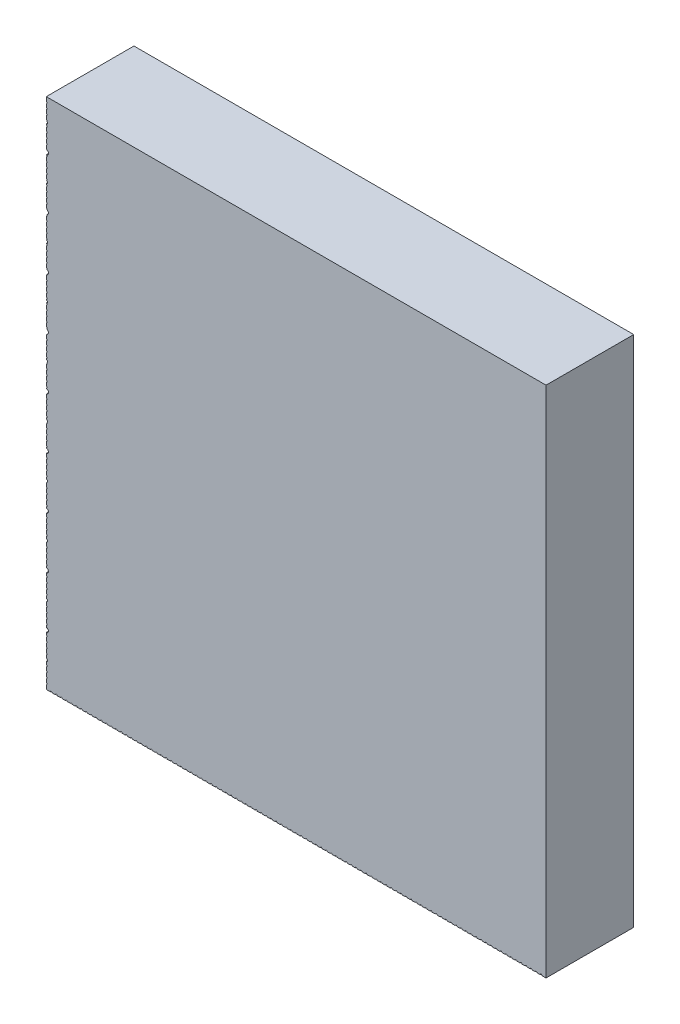
SolidWorks part; units mm, degrees
ref_plane "Front Plane" through (0, 0, 0) normal (0, 0, 1) x (1, 0, 0)
ref_plane "Top Plane" through (0, 0, 0) normal (0, 1, 0) x (1, 0, 0)
ref_plane "Right Plane" through (0, 0, 0) normal (1, 0, 0) x (0, 0, -1)
sketch "Sketch4" plane through (0, 0, 0) normal (0, 0, 1) x (1, 0, 0)
  line L1 (0, 0) -> (57, 0)
  line L2 (0, 0) -> (0, 58.5576)
  line L3 (0, 58.5576) -> (57, 58.5576)
  line L4 (57, 0) -> (57, 58.5576)
  spline S0 degree 1 poles (-4.6634, -4.7909) (51.2978, 52.6996) knots 0 0 1 1 construction
  spline S1 degree 1 poles (0, 0) (46.6344, 47.9087) knots 0.083333 0.083333 0.916667 0.916667 construction
  dimension "D1" = 57
  dimension "D2" = 58.5576
sketch "Sketch10" plane through (0, 0, 0) normal (0, 1, 0) x (1, 0, 0)
extrude "Boss-Extrude2" add sketch "Sketch4" along normal blind 10
sketch "Sketch14" plane through (0, 0, 10) normal (0, 0, 1) x (1, 0, 0)
  line L0 (0, 0) -> (57, 0) construction
  circle A0 centre (0.57, 0) radius 0.1
  spline S0 degree 1 poles (-5.7, -5.8558) (62.7, 64.4134) knots 0 0 1 1 construction
  spline S1 degree 1 poles (0, 0) (57, 58.5576) knots 0.083333 0.083333 0.916667 0.916667
  line M4 (0, 0) -> (57, 0)
  dimension "D1" = 0.2
  dimension "D2" = 0.57
extrude "Cut-Extrude1" cut sketch "Sketch14" against normal blind 10 contours A0 M4 region at (0.57, 0.0424, 10)
pattern_linear "LPattern1" count 99 spacing 0.57 along (1, 0, 0) of "Cut-Extrude1"
sketch "Sketch15" plane through (0, 0, 10) normal (0, 0, 1) x (1, 0, 0)
  line L0 (0.57, 0) -> (0.57, 0.5856)
  line L1 (0.57, 0.5856) -> (0, 0.5856)
  line L2 (0, 58.5576) -> (0, 0) construction
  circle A0 centre (0, 0.5856) radius 0.1
  spline S0 degree 1 poles (-5.7, -5.8558) (62.7, 64.4134) knots 0 0 1 1 construction
  spline S1 degree 1 poles (0, 0) (57, 58.5576) knots 0.083333 0.083333 0.916667 0.916667
  dimension "D1" = 0.2
extrude "Cut-Extrude2" cut sketch "Sketch15" against normal blind 10 contours A0 region at (-0.0972, 0.5856, 10)
pattern_linear "LPattern2" count 99 spacing 0.5856 along (0, 1, 0) of "Cut-Extrude2"
sketch "Sketch16" plane through (0, 0, 10) normal (0, 0, 1) x (1, 0, 0)
  circle A0 centre (0, 2.9279) radius 0.15
  dimension "D1" = 0.3
extrude "Cut-Extrude3" cut sketch "Sketch16" against normal blind 10
pattern_linear "LPattern3" count 19 spacing 2.95 along (0, 1, 0) of "Cut-Extrude3"
sketch "Sketch17" plane through (0, 0, 10) normal (0, 0, 1) x (1, 0, 0)
  circle A0 centre (0, 5.8779) radius 0.25
  dimension "D1" = 0.5
extrude "Cut-Extrude4" cut sketch "Sketch17" against normal blind 10
pattern_linear "LPattern4" count 9 spacing 5.9 along (0, 1, 0) of "Cut-Extrude4"
equation "\"D2@Sketch4\"=(1.0273269*\"D1@Sketch4\")"
equation "\"D1@Sketch13\"=.57*2"
equation "\"D3@LPattern2\"=0.57*1.027326895"
